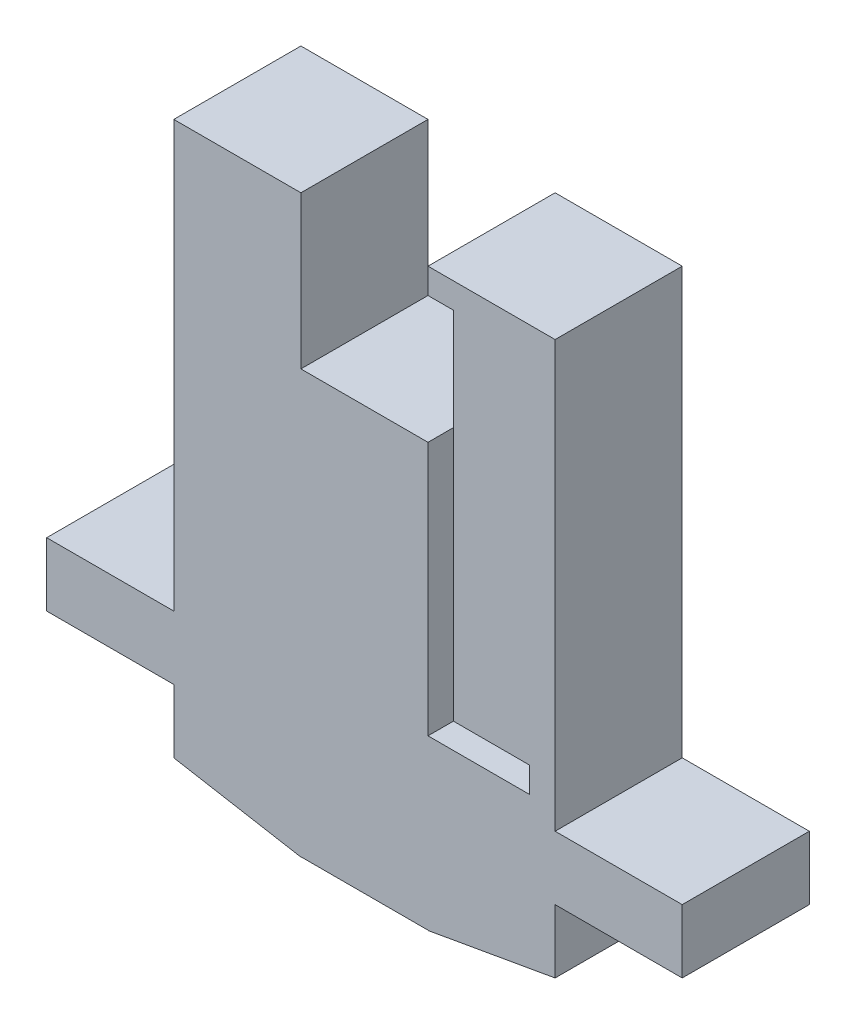
SolidWorks part; units mm, degrees
material "6061 Alloy"
ref_plane "Front Plane" through (0, 0, 0) normal (0, 0, 1) x (1, 0, 0)
ref_plane "Top Plane" through (0, 0, 0) normal (0, 1, 0) x (1, 0, 0)
ref_plane "Right Plane" through (0, 0, 0) normal (1, 0, 0) x (0, 0, -1)
sketch "Sketch2" plane through (0, 0, 0) normal (0, 0, 1) x (1, 0, 0)
  line L1 (-9.525, -15.875) -> (9.525, -15.875)
  line L2 (-9.525, -15.875) -> (-9.525, 15.875)
  line L3 (-9.525, 15.875) -> (9.525, 15.875)
  line L4 (9.525, -15.875) -> (9.525, 15.875)
  line L5 (-9.525, -15.875) -> (9.525, 15.875) construction
  line L6 (-9.525, 15.875) -> (9.525, -15.875) construction
  point P0 (0, 0)
  dimension "D1" = 31.75
  dimension "D2" = 19.05
extrude "Boss-Extrude1" add sketch "Sketch2" along normal mid plane 6.35
sketch "Sketch4" plane through (-1.5069, 3.1105, 3.175) normal (0, 0, 1) x (1, 0, 0)
  line L1 (-1.6681, 12.7645) -> (4.6819, 12.7645)
  line L2 (-1.6681, 12.7645) -> (-1.6681, 2.6045)
  line L3 (-1.6681, 2.6045) -> (4.6819, 2.6045)
  line L4 (4.6819, 12.7645) -> (4.6819, 2.6045)
  line L7 (-8.0181, 12.7645) -> (11.0319, 12.7645)
  line L8 (-8.0181, 12.7645) -> (-8.0181, 10.2245)
  line L9 (-8.0181, 10.2245) -> (11.0319, 10.2245)
  line L10 (11.0319, 12.7645) -> (11.0319, 10.2245)
  line L11 (11.0319, 12.7645) -> (-8.0181, 12.7645) construction
  line L12 (11.0319, -18.9855) -> (11.0319, 12.7645) construction
  line L13 (-8.0181, 12.7645) -> (-8.0181, -18.9855) construction
  dimension "D1" = 6.35
  dimension "D2" = 0
  dimension "D3" = 10.16
  dimension "D4" = 2.54
  dimension "D5" = 0
  dimension "D6" = 0
  dimension "D7" = 0
  dimension "D8" = 6.35
extrude "Cut-Extrude1" cut sketch "Sketch4" against normal through all contours L4 L9 | L2 L9 L4 | L9 L2 L3 L4 | L9 L2 region at (0, 14.605, 3.175) region at (-6.35, 14.605, 3.175) region at (6.35, 14.605, 3.175) region at (0, 9.525, 3.175)
sketch "Sketch6" plane through (-1.5069, 3.1105, 3.175) normal (0, 0, 1) x (1, 0, 0)
  line L0 (4.6819, 10.2245) -> (4.6819, 2.6045) construction
  line L5 (4.6819, 8.9545) -> (5.9519, 8.9545)
  line L6 (4.6819, 8.9545) -> (4.6819, -10.0955)
  line L7 (4.6819, -10.0955) -> (5.9519, -10.0955)
  line L8 (5.9519, 8.9545) -> (5.9519, -10.0955)
  line L12 (4.6819, -10.0955) -> (9.7619, -10.0955)
  line L13 (4.6819, -10.0955) -> (4.6819, -8.8255)
  line L14 (4.6819, -8.8255) -> (9.7619, -8.8255)
  line L15 (9.7619, -10.0955) -> (9.7619, -8.8255)
  line L16 (4.6819, 10.2245) -> (11.0319, 10.2245) construction
  line L17 (-8.0181, -18.9855) -> (11.0319, -18.9855) construction
  line L18 (11.0319, -18.9855) -> (11.0319, 10.2245) construction
  point P7 (5.3169, -10.0955)
  dimension "D1" = 1.27
  dimension "D2" = 1.27
  dimension "D3" = 8.89
  dimension "D4" = 1.27
  dimension "D5" = 1.27
extrude "Cut-Extrude2" cut sketch "Sketch6" against normal through all contours L6 L14 L8 L5 | L14 L6 L7 L8 | L12 L15 L14 L8 region at (3.81, 3.175, 3.175) region at (3.81, -6.35, 3.175) region at (6.35, -6.35, 3.175)
sketch "Sketch7" plane through (0, 0, 3.175) normal (0, 0, 1) x (1, 0, 0)
  line L0 (-9.525, -14.2875) -> (-0.5218, -15.875)
  line L1 (-9.525, 13.335) -> (-9.525, -15.875) construction
  line L2 (-9.525, -15.875) -> (9.525, -15.875) construction
  line L3 (-0.5218, -15.875) -> (-9.525, -15.875)
  line L4 (-9.525, -15.875) -> (-9.525, -14.2875)
  dimension "D1" = 1.5875
  dimension "D2" = 80
extrude "Cut-Extrude3" cut sketch "Sketch7" against normal through all
mirror "Mirror1" about plane through (0, 0, 0) normal (1, 0, 0) of "Cut-Extrude3"
sketch "Sketch8" plane through (0, 0, 3.175) normal (0, 0, 1) x (1, 0, 0)
  line L0 (-9.525, 13.335) -> (-9.525, -14.2875) construction
  line L1 (-9.525, -7.9375) -> (-15.875, -7.9375)
  line L2 (-9.525, -7.9375) -> (-9.525, -11.1125)
  line L3 (-9.525, -11.1125) -> (-15.875, -11.1125)
  line L4 (-15.875, -7.9375) -> (-15.875, -11.1125)
  dimension "D1" = 6.35
  dimension "D2" = 3.175
  dimension "D3" = 3.175
extrude "Boss-Extrude2" add sketch "Sketch8" against normal blind 6.35
mirror "Mirror3" about plane through (0, 0, 0) normal (1, 0, 0) of "Boss-Extrude2"
sketch "Sketch9" plane through (0, 0, 3.175) normal (0, 0, 1) x (1, 0, 0)
  line L1 (-3.175, -15.3931) -> (3.175, -15.3931)
  line L2 (-3.175, -15.3931) -> (-3.175, -16.6935)
  line L3 (-3.175, -16.6935) -> (3.175, -16.6935)
  line L4 (3.175, -15.3931) -> (3.175, -16.6935)
  line L5 (-3.175, -15.3931) -> (3.175, -16.6935) construction
  line L6 (-3.175, -16.6935) -> (3.175, -15.3931) construction
  point P0 (0, -16.0433)
  dimension "D1" = 6.35
  dimension "D2" = 3.175
extrude "Cut-Extrude4" cut sketch "Sketch9" against normal through all
